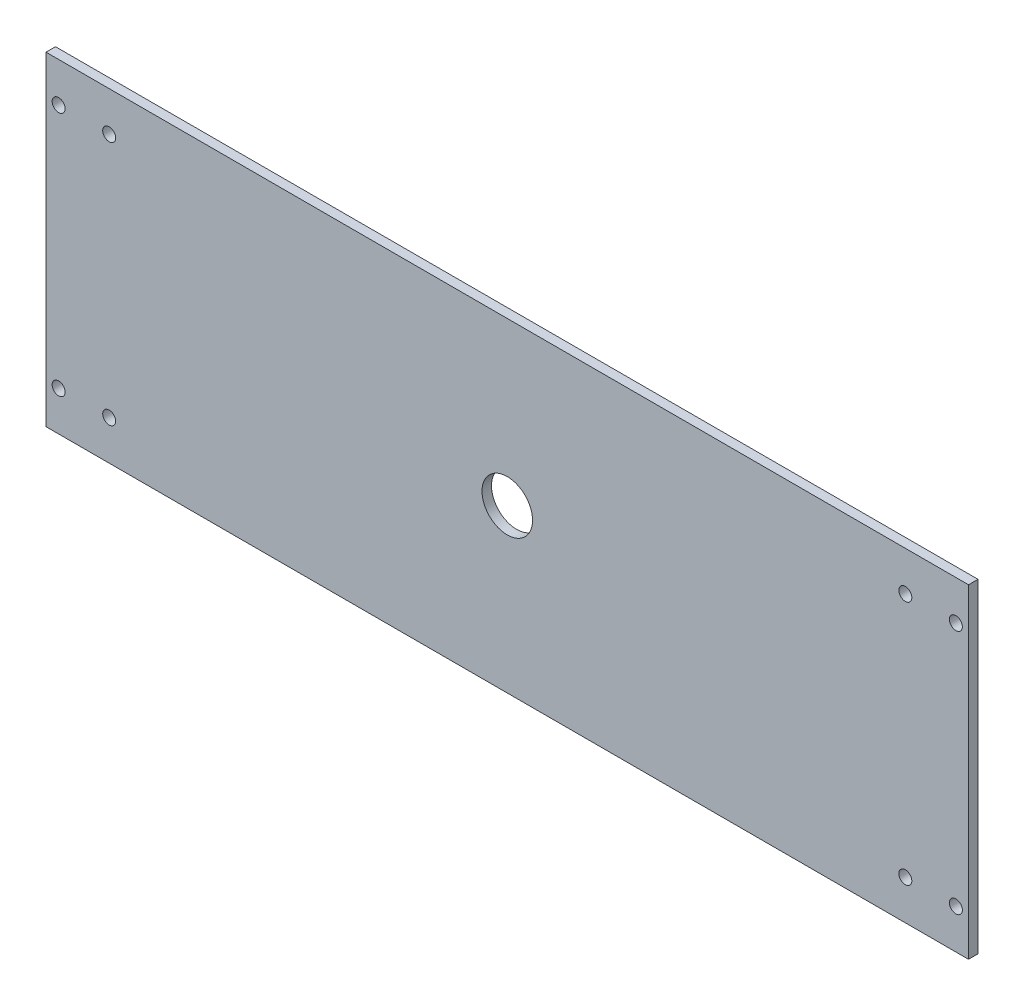
SolidWorks part; units mm, degrees
material "E-Glass Fiber"
ref_plane "Front Plane" through (0, 0, 0) normal (0, 0, 1) x (1, 0, 0)
ref_plane "Top Plane" through (0, 0, 0) normal (0, 1, 0) x (1, 0, 0)
ref_plane "Right Plane" through (0, 0, 0) normal (1, 0, 0) x (0, 0, -1)
sketch "Sketch1" plane through (0, 0, 0) normal (0, 0, 1) x (1, 0, 0)
  line L1 (-115.8875, -40.748) -> (115.8875, -40.748)
  line L2 (-115.8875, -40.748) -> (-115.8875, 40.7479)
  line L3 (-115.8875, 40.7479) -> (115.8875, 40.7479)
  line L4 (115.8875, -40.748) -> (115.8875, 40.7479)
  line L5 (-115.8875, -40.748) -> (115.8875, 40.7479) construction
  line L6 (-115.8875, 40.7479) -> (115.8875, -40.748) construction
  point P0 (0, 0)
  dimension "D1" = 231.775
  dimension "D2" = 81.4959
extrude "Boss-Extrude1" add sketch "Sketch1" along normal blind 2.3813
sketch "Sketch2" plane through (0, 0, 2.3813) normal (0, 0, 1) x (1, 0, 0)
  line L0 (-8.9154, 28.575) -> (29.1846, 28.575) construction
  line L1 (115.8875, 0) -> (111.125, 0) construction
  line L2 (115.8875, -40.748) -> (115.8875, 40.7479) construction
  line L3 (111.125, 0) -> (111.125, 9.525) construction
  line L4 (111.125, 9.525) -> (111.125, 25.4) construction
  line L5 (-115.8875, 0) -> (-111.125, 0) construction
  line L6 (-115.8875, 40.7479) -> (-115.8875, -40.748) construction
  line L7 (-111.125, 0) -> (-111.125, 9.525) construction
  line L8 (-111.125, 9.525) -> (-111.125, 25.4) construction
  line L9 (-115.8875, 30.8204) -> (-112.7125, 30.8204) construction
  line L10 (-112.7125, 30.8204) -> (-100.0125, 30.8204) construction
  dimension "D1" = 38.1
  dimension "D2" = 28.575
  dimension "D3" = 8.9154
  dimension "D4" = 4.7625
  dimension "D5" = 9.525
  dimension "D6" = 25.4
  dimension "D7" = 30.8204
  dimension "D8" = 12.7
  dimension "D9" = 3.175
hole_wizard "#4 Clearance Hole2" positions "Sketch6" profile "Sketch7" hole size "#4" standard "ANSI Inch" end condition through all
sketch "Sketch6" plane through (0, 0, 2.3813) normal (0, 0, 1) x (1, 0, 0)
  point P0 (-112.7125, 30.8204)
  point P3 (-100.0125, 30.8204)
sketch "Sketch7" plane through (-112.7125, 30.8204, 2.3813) normal (1, 0, 0) x (0, -1, 0)
  line L0 (0, 0) -> (0, 2.3813)
  line L1 (0, 2.3813) -> (1.6319, 2.3813)
  line L2 (1.6319, 2.3813) -> (1.6319, 0)
  line L5 (1.6319, 0) -> (0, 0)
  line L11 (0, -6.35) -> (0, 107.95) construction
  dimension "Thru Hole Dia." = 3.2639
  dimension "Thru Hole Depth" = 2.3813
mirror "Mirror2" about plane through (0, 0, 0) normal (1, 0, 0) of "#4 Clearance Hole2"
mirror "Mirror3" about plane through (0, 0, 0) normal (0, 1, 0) of "Mirror2"
hole_wizard "1/2 (0.5) Diameter Hole1" positions "Sketch9" profile "Sketch8" hole size "1/2" standard "ANSI Inch" end condition through all
sketch "Sketch9" plane through (0, 0, 2.3813) normal (0, 0, 1) x (1, 0, 0)
  point P0 (0, 0)
sketch "Sketch8" plane through (0, 0, 2.3813) normal (1, 0, 0) x (0, -1, 0)
  line L0 (0, 0) -> (0, 2.3812)
  line L1 (0, 2.3812) -> (6.35, 2.3812)
  line L2 (6.35, 2.3812) -> (6.35, 0)
  line L5 (6.35, 0) -> (0, 0)
  line L11 (0, -6.35) -> (0, 107.95) construction
  dimension "Thru Hole Dia." = 12.7
  dimension "Thru Hole Depth" = 2.3813
